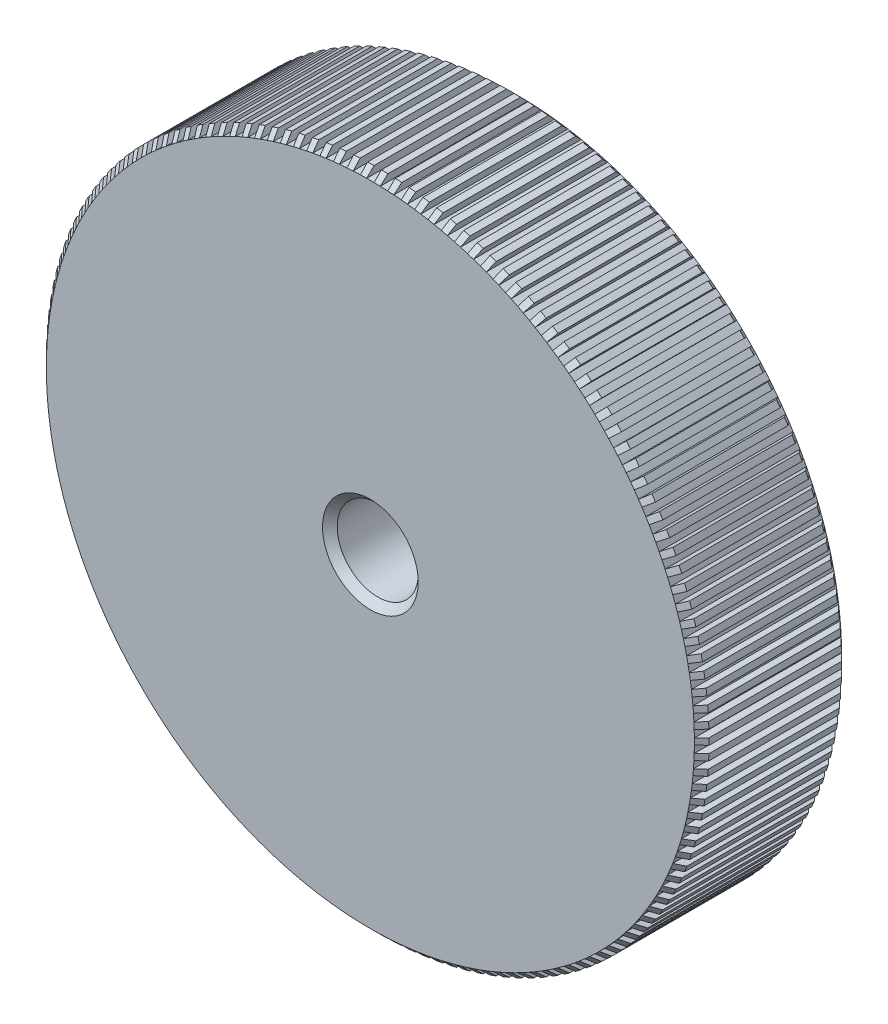
SolidWorks part; units mm, degrees
ref_plane "前视基准面" through (0, 0, 0) normal (0, 0, 1) x (1, 0, 0)
ref_plane "上视基准面" through (0, 0, 0) normal (0, 1, 0) x (1, 0, 0)
ref_plane "右视基准面" through (0, 0, 0) normal (1, 0, 0) x (0, 0, -1)
sketch "草图1" plane through (0, 0, 0) normal (0, 0, 1) x (1, 0, 0)
  circle A0 centre (0, 0) radius 4.5
  dimension "D1" = 9
extrude "凸台-拉伸1" add sketch "草图1" against normal blind 2
sketch "草图8" plane through (0, 0, -2) normal (0, 0, -1) x (-1, 0, 0)
  circle A0 centre (0, 0) radius 0.55
  dimension "D1" = 1.1
extrude "切除-拉伸1" cut sketch "草图8" against normal through all contours A0
chamfer "倒角1" distance 0.1 angle 45 4 edges at (-0.55, 0, -2) (4.5, 0, -2) (4.5, 0, 0) (-0.55, 0, 0)
sketch "草图7" plane through (0, 0, 0) normal (0, 0, 1) x (1, 0, 0)
  line L1 (-0.05, -4.9868) -> (0.05, -4.9868)
  line L2 (-0.05, -4.9868) -> (-0.05, 4.9868)
  line L3 (-0.05, 4.9868) -> (0.05, 4.9868)
  line L4 (0.05, -4.9868) -> (0.05, 4.9868)
  line L5 (-0.05, -4.9868) -> (0.05, 4.9868) construction
  line L6 (-0.05, 4.9868) -> (0.05, -4.9868) construction
  circle A1 centre (0, 0) radius 4.4
  circle A2 centre (0, 0) radius 4.5 construction
  point P0 (0, 0)
  circle M13 centre (0, 0) radius 4.4
  dimension "D3" = 0.1
  dimension "D2" = 0.1
extrude "切除-拉伸3" cut sketch "草图7" against normal through all contours L4 L3 L2 M13 region at (0, 4.6933, 0)
pattern_circular "阵列(圆周)1" count 150 over 360 about axis through (0, 0, -2) along (0, 0, 1) of "切除-拉伸3" reverse direction yes
